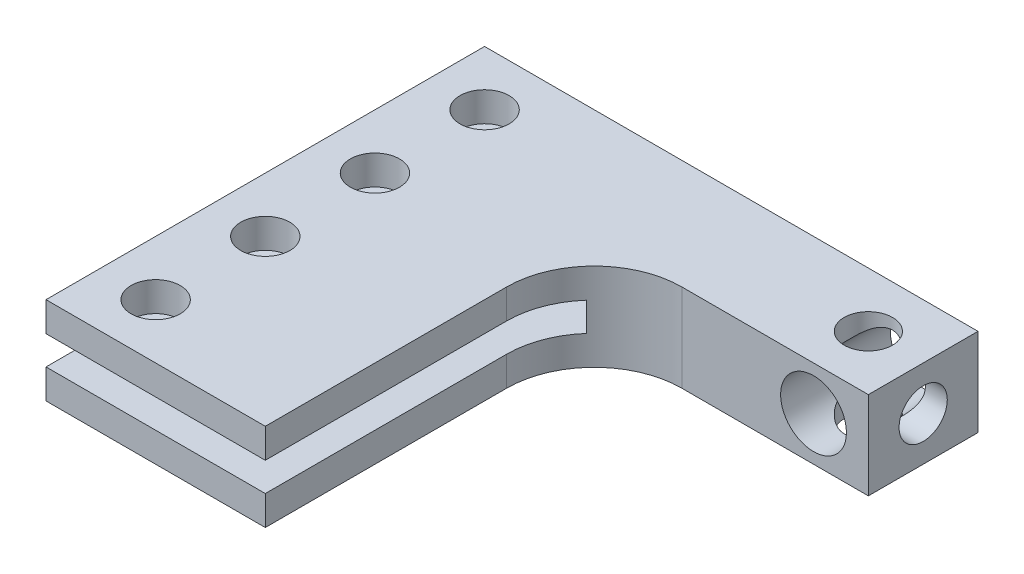
SolidWorks part; units mm, degrees
ref_plane "Front Plane" through (0, 0, 0) normal (0, 0, 1) x (1, 0, 0)
ref_plane "Top Plane" through (0, 0, 0) normal (0, 1, 0) x (1, 0, 0)
ref_plane "Right Plane" through (0, 0, 0) normal (1, 0, 0) x (0, 0, -1)
sketch "Sketch1" plane through (0, 0, 0) normal (0, 1, 0) x (1, 0, 0)
  line L0 (-33.097, 5.3879) -> (-20.397, 5.3879)
  line L2 (-20.397, 5.3879) -> (-4.522, 5.3879)
  line L3 (-4.522, 5.3879) -> (-4.522, -0.9621)
  line L4 (-4.522, -0.9621) -> (-20.397, -0.9621)
  line L5 (-20.397, -0.9621) -> (-20.397, -20.0121)
  line L6 (-20.397, -20.0121) -> (-33.097, -20.0121)
  line L7 (-33.097, -20.0121) -> (-33.097, 5.3879)
  dimension "D1" = 25.4
  dimension "D2" = 12.7
  dimension "D3" = 6.35
  dimension "D4" = 15.875
extrude "Boss-Extrude1" add sketch "Sketch1" along normal blind 5.08
sketch "Sketch2" plane through (-33.097, 0, 0) normal (-1, 0, 0) x (0, 0, 1)
  line L0 (-5.3879, 5.08) -> (-5.3879, 0) construction
  line L1 (-5.3879, 3.3735) -> (20.0121, 3.3735)
  line L2 (-5.3879, 3.3735) -> (-5.3879, 1.7065)
  line L3 (-5.3879, 1.7065) -> (20.0121, 1.7065)
  line L4 (20.0121, 3.3735) -> (20.0121, 1.7065)
  line L5 (20.0121, 5.08) -> (20.0121, 0) construction
  line L6 (7.3121, 5.08) -> (7.3121, 3.3735) construction
  line L7 (-5.3879, 5.08) -> (20.0121, 5.08) construction
  line L8 (7.3121, 1.7065) -> (7.3121, 0) construction
  line L9 (-5.3879, 0) -> (20.0121, 0) construction
  dimension "D1" = 1.6669
extrude "Cut-Extrude1" cut sketch "Sketch2" against normal blind 13.97
sketch "Sketch3" plane through (0, 5.08, 0) normal (0, 1, 0) x (1, 0, 0)
  line L0 (-33.097, 5.3879) -> (-33.097, -20.0121) construction
  line L2 (-33.097, -20.0121) -> (-20.397, -20.0121) construction
  circle A0 centre (-29.922, -16.8371) radius 1.4224
  circle A1 centre (-29.922, -10.4871) radius 1.4224
  circle A2 centre (-29.922, -4.1371) radius 1.4224
  circle A3 centre (-29.922, 2.2129) radius 1.4224
  dimension "D1" = 2.8448
  dimension "D4" = 4
  dimension "D2" = 3.175
  dimension "D3" = 3.175
  dimension "D5" = 6.35
extrude "Cut-Extrude2" cut sketch "Sketch3" against normal blind 12.7
sketch "Sketch5" plane through (0, 0, 0.9621) normal (0, 0, 1) x (1, 0, 0)
  line L2 (-9.602, 2.54) -> (-9.602, 5.4864) construction
  circle A1 centre (-7.697, 2.54) radius 1.905
  dimension "D1" = 3.81
extrude "Cut-Extrude3" cut sketch "Sketch5" against normal blind 12.7
fillet "Fillet3" radius 5.08 2 edges at (-20.397, 4.2267, 0.9621) (-20.397, 0.8533, 0.9621)
sketch "Sketch6" plane through (-4.522, 0, 0) normal (1, 0, 0) x (0, 0, -1)
  line L0 (2.2129, 5.08) -> (2.2129, 0) construction
  line L1 (3.6353, 5.08) -> (0.7905, 5.08) construction
  line L2 (-0.9621, 0) -> (5.3879, 0) construction
  circle A0 centre (2.2129, 2.54) radius 1.397
  point P9 (2.2129, 2.54)
  dimension "D1" = 2.794
extrude "Cut-Extrude4" cut sketch "Sketch6" against normal up to next
sketch "Sketch7" plane through (0, 5.08, 0) normal (0, 1, 0) x (1, 0, 0)
  line L0 (-7.697, -0.9621) -> (-7.697, 5.3879) construction
  line L2 (-4.522, 5.3879) -> (-33.097, 5.3879) construction
  circle A0 centre (-7.697, 2.2129) radius 1.397
  point P2 (0, 0)
  point P3 (0, 0)
  point P8 (0, 0)
  dimension "D1" = 2.794
extrude "Cut-Extrude5" cut sketch "Sketch7" against normal through all and the other way through all
equation "\"bolt_hole\"= .112in'holes for screws"
